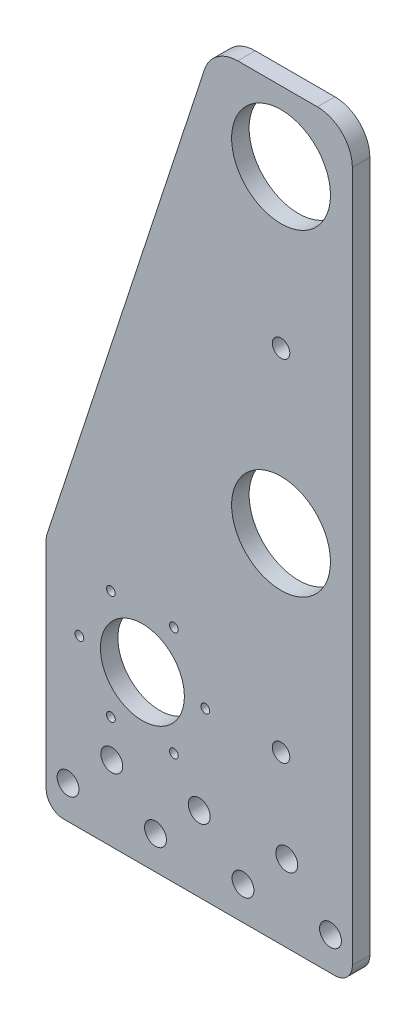
SolidWorks part; units mm, degrees
ref_plane "Front Plane" through (0, 0, 0) normal (0, 0, 1) x (1, 0, 0)
ref_plane "Top Plane" through (0, 0, 0) normal (0, 1, 0) x (1, 0, 0)
ref_plane "Right Plane" through (0, 0, 0) normal (1, 0, 0) x (0, 0, -1)
sketch "Sketch1" plane through (0, 0, 0) normal (0, 0, 1) x (1, 0, 0)
  line L2 (88.9, 205.74) -> (88.9, 5.08)
  line L3 (83.82, 0) -> (5.08, 0)
  line L4 (78.74, 215.9) -> (55.6253, 215.9)
  line L5 (45.9692, 208.9) -> (0.252, 69.2)
  line L6 (0, 67.62) -> (0, 5.08)
  line L7 (6.35, 9.652) -> (31.75, 9.652) construction
  line L8 (27.94, 48.354) -> (27.94, 84.1044) construction
  line L9 (27.94, 48.354) -> (60.7143, 48.354) construction
  circle A0 centre (68.199, 195.58) radius 14.351
  circle A1 centre (68.199, 103.378) radius 14.351
  circle A2 centre (68.199, 149.954) radius 2.54
  circle A3 centre (68.199, 48.354) radius 2.54
  arc A4 (78.74, 215.9) -> (88.9, 205.74) centre (78.74, 205.74) cw
  arc A5 (0, 5.08) -> (5.08, 0) centre (5.08, 5.08) ccw
  arc A6 (88.9, 5.08) -> (83.82, 0) centre (83.82, 5.08) cw
  arc A7 (55.6253, 215.9) -> (45.9692, 208.9) centre (55.6253, 205.74) ccw
  arc A8 (0.252, 69.2) -> (0, 67.62) centre (5.08, 67.62) ccw
  circle A9 centre (27.94, 48.354) radius 12.192
  circle A17 centre (68.199, 195.58) radius 50.8 construction
  circle A18 centre (68.199, 103.378) radius 38.1 construction
  circle A19 centre (6.35, 9.652) radius 3.175
  circle A21 centre (31.75, 9.652) radius 3.175
  circle A22 centre (57.15, 9.652) radius 3.175
  circle A23 centre (82.55, 9.652) radius 3.175
  circle A29 centre (69.85, 22.352) radius 3.175
  circle A30 centre (44.45, 21.844) radius 3.175
  circle A31 centre (19.05, 21.844) radius 3.175
  circle A32 centre (46.228, 48.354) radius 1.27
  circle A33 centre (37.084, 32.5161) radius 1.27
  circle A34 centre (18.796, 32.5161) radius 1.27
  circle A35 centre (9.652, 48.354) radius 1.27
  circle A36 centre (18.796, 64.1919) radius 1.27
  circle A37 centre (37.084, 64.1919) radius 1.27
  point P17 (88.9, 215.9)
  point P20 (0, 0)
  point P23 (88.9, 0)
  point P25 (48.26, 215.9)
  point P26 (48.26, 215.9)
  point P43 (27.94, 48.354)
  point P67 (27.94, 48.354)
  dimension "D1" = 28.702
  dimension "D2" = 28.702
  dimension "D4" = 88.9
  dimension "D7" = 5.08
  dimension "D9" = 5.08
  dimension "D11" = 10.16
  dimension "D12" = 5.08
  dimension "D13" = 10.16
  dimension "D14" = 5.08
  dimension "D16" = 24.384
  dimension "D17" = 18.288
  dimension "D23" = 139.7
  dimension "D24" = 101.6
  dimension "D25" = 76.2
  dimension "D26" = 6.35
  dimension "D29" = 21.844
  dimension "D31" = 6.35
  dimension "D32" = 4
  dimension "D34" = 19.05
  dimension "D39" = 21.844
  dimension "D30" = 6.35
  dimension "D35" = 6.35
  dimension "D37" = 6.35
  dimension "D38" = 25.4
  dimension "D18" = 2.54
  dimension "D3" = 92.202
  dimension ".75" = 20.701
  dimension "D5" = 215.9
  dimension "D6" = 20.32
  dimension "D8" = 45.626
  dimension "D10" = 101.6
  dimension "D15" = 40.64
  dimension "D20" = 27.94
  dimension "D27" = 9.652
  dimension "D28" = 25.4
  dimension "D33" = 12.7
  dimension "D36" = 25.4
  dimension "D19" = 6
extrude "Boss-Extrude1" add sketch "Sketch1" along normal blind 5.08
